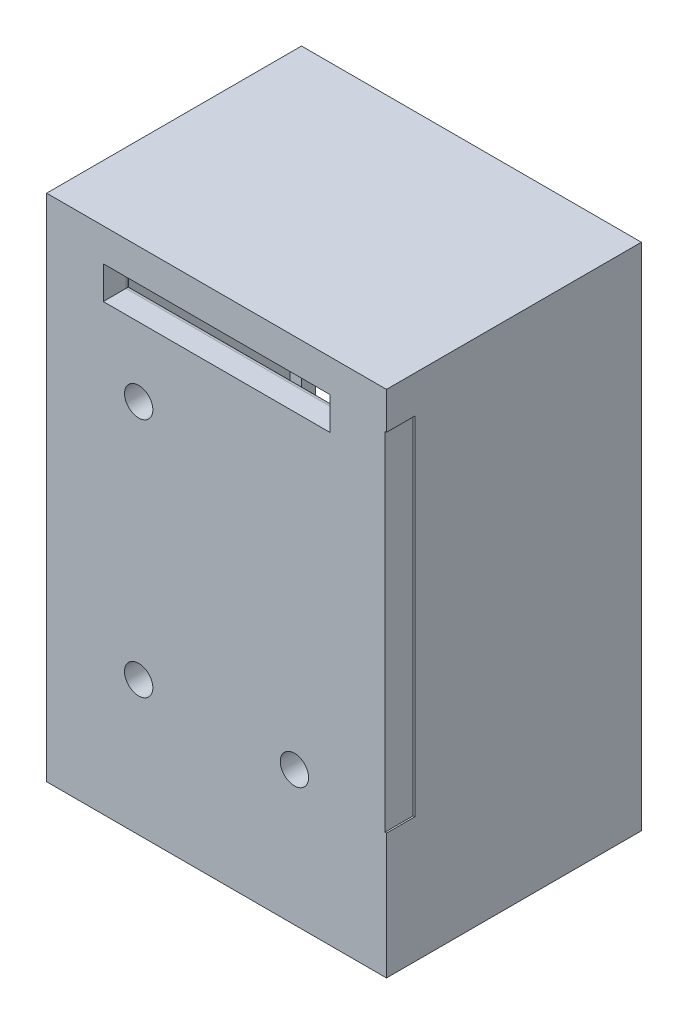
SolidWorks part; units mm, degrees
ref_plane "Plan de face" through (0, 0, 0) normal (0, 0, 1) x (1, 0, 0)
ref_plane "Plan de dessus" through (0, 0, 0) normal (0, 1, 0) x (1, 0, 0)
ref_plane "Plan de droite" through (0, 0, 0) normal (1, 0, 0) x (0, 0, -1)
sketch "Esquisse1" plane through (0, 0, 0) normal (0, 0, 1) x (1, 0, 0)
  line L0 (-42.5, 42.5) -> (0, 0)
  line L1 (-50, 50) -> (50, 50)
  line L2 (-50, 50) -> (-50, -50)
  line L3 (-50, -50) -> (50, -50)
  line L4 (50, 50) -> (50, -50)
  line L5 (-50, 50) -> (50, -50) construction
  line L6 (-50, -50) -> (50, 50) construction
  line L7 (-42.5, 42.5) -> (42.5, 42.5)
  line L8 (-42.5, 42.5) -> (-42.5, -42.5)
  line L9 (-42.5, -42.5) -> (42.5, -42.5)
  line L10 (42.5, 42.5) -> (42.5, -42.5)
  line L11 (-42.5, 42.5) -> (42.5, -42.5) construction
  line L12 (-42.5, -42.5) -> (42.5, 42.5) construction
  line L13 (0, 0) -> (42.5, -42.5)
  line L14 (-42.5, -42.5) -> (0, 0)
  line L15 (0, 0) -> (42.5, 42.5)
  line L16 (-42.5, 42.5) -> (-50, 42.5)
  line L17 (-50, 42.5) -> (-42.5, 50)
  line L18 (-42.5, 50) -> (-42.5, 42.5)
  line L19 (-46.25, 46.25) -> (-44.4822, 48.0178)
  line L20 (-46.25, 46.25) -> (-48.0178, 44.4822)
  line L21 (44.4822, -48.0178) -> (-47.9542, 44.5507)
  line L22 (44.4822, -48.0178) -> (47.9542, -44.5507)
  line L23 (-47.9542, 44.5507) -> (-44.4822, 48.0178)
  line L24 (47.9542, -44.5507) -> (-44.4822, 48.0178)
  line L25 (44.4822, -48.0178) -> (-44.4822, 48.0178) construction
  line L26 (-47.9542, 44.5507) -> (47.9542, -44.5507) construction
  line L27 (42.5, 42.5) -> (42.5, 50)
  line L28 (42.5, 42.5) -> (50, 42.5)
  line L29 (50, 42.5) -> (42.5, 50)
  line L30 (46.25, 46.25) -> (44.3148, 48.1852)
  line L31 (46.25, 46.25) -> (47.8504, 44.6496)
  line L32 (-44.3148, -48.1852) -> (48.1852, 44.3148)
  line L33 (-44.3148, -48.1852) -> (-48.1852, -44.3148)
  line L34 (48.1852, 44.3148) -> (44.3148, 48.1852)
  line L35 (-48.1852, -44.3148) -> (44.3148, 48.1852)
  line L36 (-44.3148, -48.1852) -> (44.3148, 48.1852) construction
  line L37 (48.1852, 44.3148) -> (-48.1852, -44.3148) construction
  circle A0 centre (0, 0) radius 29
  circle A1 centre (0, 0) radius 34
  point P0 (0, 0)
  point P6 (0, 0)
  dimension "D5" = 58
  dimension "D6" = 68
  dimension "D1" = 100
  dimension "D2" = 100
  dimension "D3" = 85
  dimension "D4" = 85
  dimension "D7" = 2.5
  dimension "D8" = 2.5
  dimension "D9" = 5
extrude "Boss.-Extru.2" add sketch "Esquisse1" along normal blind 10 contours L7 L35 L27 L1 L18 L24 | L33 L35 L8 L21 L16 L2 L3 L4 L28 L32 L10 L24 L22 L9 | L21 A1 L35 A0 | L32 A1 L21 A0 | L35 A1 L24 A0 | L24 A1 L32 A0 | A1 L32 L10 L15 | A1 L15 L7 L35 | L15 A1 L35 A0 | L32 A1 L15 A0 | L24 A1 L0 A0 | A1 L24 L7 L0 | L0 A1 L21 A0 | L21 A1 L13 A0 | L13 A1 L24 A0 | A1 L13 L10 L24 | A1 L21 L9 L13 | L22 L24 L10 L9 L21 | L35 L33 L32 L9 L8 | A1 L35 L8 L14 | A1 L14 L9 L32 | L35 A1 L14 A0 | L14 A1 L32 A0 | A1 L0 L8 L21 | L21 L8 L16 | L7 L24 L18 | L18 L24 L17 L20 L21 L16 | L16 L21 L17 | L21 L23 L17 L1 L2 | L24 L18 L17 | L27 L35 L29 | L35 L27 L28 L32 L29 | L32 L28 L29 | L29 L4 L1 | L10 L32 L28 | L35 L7 L27 | L16 L17 L18 region at (-31.9722, 33.7018, 0) region at (-41.3241, 43.6776, 0) region at (-33.6728, 31.9878, 0) region at (-43.6355, 41.3629, 0) region at (-44.7427, 44.7878, 0) region at (-21.3754, 23.1269, 0) region at (-23.111, 21.3913, 0) region at (-0.082, 46.3052, 0) region at (-43.8622, 0.2295, 0) region at (-47.9527, 43.1828, 0) region at (-43.1607, 48.0168, 0) region at (-0.1204, 29.0381, 0) region at (-29.033, 0.1411, 0) region at (41.2099, 43.7901, 0) region at (31.8324, 33.7334, 0) region at (-33.7334, -31.8324, 0) region at (-43.8581, -43.8581, 0) region at (-47.5002, 47.5005, 0) region at (21.2774, 23.2138, 0) region at (-23.2138, -21.2774, 0) region at (43.7901, 41.2099, 0) region at (33.7334, 31.8324, 0) region at (44.8027, 44.8027, 0) region at (43.1049, 48.1852, 0) region at (-31.8324, -33.7334, 0) region at (47.5, 47.5, 0) region at (23.2138, 21.2774, 0) region at (-21.2774, -23.2138, 0) region at (48.1852, 43.1049, 0) region at (29.033, -0.1411, 0) region at (0.1204, -29.0381, 0) region at (43.8779, -43.9513, 0) region at (33.6728, -31.9878, 0) region at (31.9722, -33.7018, 0) region at (23.111, -21.3913, 0) region at (21.3754, -23.1269, 0)
sketch "Esquisse2" plane through (0, 50, 0) normal (0, 1, 0) x (-1, 0, 0)
  line L0 (50, 5) -> (-50, 5)
  line L1 (50, 10) -> (50, 0) construction
  line L2 (-50, 10) -> (-50, 0) construction
  line L4 (2.5, 7.5) -> (-2.5, 7.5)
  line L5 (2.5, 7.5) -> (2.5, 2.5)
  line L6 (2.5, 2.5) -> (-2.5, 2.5)
  line L7 (-2.5, 7.5) -> (-2.5, 2.5)
  line L8 (2.5, 7.5) -> (-2.5, 2.5) construction
  line L9 (2.5, 2.5) -> (-2.5, 7.5) construction
  point P6 (0, 5)
  dimension "D1" = 5
  dimension "D2" = 5
extrude "Boss.-Extru.3" add sketch "Esquisse2" along normal blind 5 contours L0 L7 L6 L5 | L4 L7 L0 L5 region at (0, 50, 3.75) region at (0, 50, 6.25)
sketch "Esquisse3" plane through (0, 55, 0) normal (0, 1, 0) x (-1, 0, 0)
  line L0 (2.5, 5) -> (-2.5, 5)
  line L1 (2.5, 7.5) -> (2.5, 2.5) construction
  line L2 (-2.5, 7.5) -> (-2.5, 2.5) construction
  line L3 (2.5, 5) -> (2.5, 4)
  line L4 (2.5, 4) -> (-2.5, 4)
  line L5 (-2.5, 4) -> (-2.5, 5)
  line L6 (2.5, 5) -> (2.5, 6)
  line L7 (2.5, 6) -> (-2.5, 6)
  line L8 (-2.5, 6) -> (-2.5, 5)
  line M1 (2.5, 2.5) -> (2.5, 7.5)
  line M3 (-2.5, 7.5) -> (-2.5, 2.5)
  dimension "D1" = 1
  dimension "D2" = 1
extrude "Enlèv. mat.-Extru.1" cut sketch "Esquisse3" against normal blind 2 contours L4 L0 M1 M3 | L7 L0 M1 M3 region at (0, 55, 4.5) region at (0, 55, 5.5)
sketch "Esquisse4" plane through (-2.5, 0, 0) normal (-1, 0, 0) x (0, 0, 1)
  line L0 (6, 53) -> (6, 68)
  line L1 (6, 53) -> (4, 53)
  line L2 (4, 53) -> (4, 68)
  line L3 (4, 68) -> (6, 68)
  dimension "D1" = 15
extrude "Boss.-Extru.4" add sketch "Esquisse4" along normal blind 50 and the other way blind 55
sketch "Esquisse5" plane through (0, 0, 6) normal (0, 0, 1) x (1, 0, 0)
  line L0 (52.5, 60.5) -> (12.5, 60.5)
  line L1 (52.5, 53) -> (52.5, 68) construction
  line L2 (-52.5, 60.5) -> (-12.5, 60.5)
  line L3 (52.5, 58.5) -> (12.5, 58.5)
  line L4 (52.5, 58.5) -> (52.5, 62.5)
  line L5 (52.5, 62.5) -> (12.5, 62.5)
  line L6 (12.5, 58.5) -> (12.5, 62.5)
  line L7 (52.5, 58.5) -> (12.5, 62.5) construction
  line L8 (52.5, 62.5) -> (12.5, 58.5) construction
  line L9 (-52.5, 53) -> (-52.5, 68) construction
  line L11 (-52.5, 58.5) -> (-12.5, 58.5)
  line L12 (-52.5, 58.5) -> (-52.5, 62.5)
  line L13 (-52.5, 62.5) -> (-12.5, 62.5)
  line L14 (-12.5, 58.5) -> (-12.5, 62.5)
  line L15 (-52.5, 58.5) -> (-12.5, 62.5) construction
  line L16 (-52.5, 62.5) -> (-12.5, 58.5) construction
  point P4 (32.5, 60.5)
  point P13 (-32.5, 60.5)
  point P14 (-32.5, 60.5)
  line M8 (-52.5, 68) -> (-52.5, 53)
  dimension "D1" = 4
  dimension "D2" = 40
  dimension "D3" = 40
  dimension "D4" = 4
extrude "Enlèv. mat.-Extru.2" cut sketch "Esquisse5" against normal blind 1 contours L2 L14 L13 M8 | L11 L14 L2 M8 | L6 L0 L4 L5 | L6 L3 L4 L0 region at (32.5, 59.5, 6) region at (32.5, 61.5, 6) region at (-32.5, 61.5, 6) region at (-32.5, 59.5, 6)
sketch "Esquisse6" plane through (0, 0, 6) normal (0, 0, 1) x (1, 0, 0)
  line L0 (-52.5, 58.5) -> (-12.5, 58.5) construction
  line L1 (-12.5, 58.5) -> (-32.5, 58.5) construction
  line L2 (-32.5, 58.5) -> (-32.5, 62.5) construction
  line L3 (-52.5, 62.5) -> (-12.5, 62.5) construction
  line L4 (-32.5, 58.5) -> (-12.5, 58.5) construction
  line L5 (-12.5, 58.5) -> (-22.5, 58.5) construction
  line L6 (-22.5, 58.5) -> (-22.5, 62.5) construction
  line L7 (-52.5, 58.5) -> (-32.5, 58.5) construction
  line L8 (-42.5, 58.5) -> (-42.5, 62.5) construction
  line L9 (12.5, 58.5) -> (52.5, 58.5) construction
  line L10 (52.5, 58.5) -> (32.5, 58.5) construction
  line L11 (32.5, 58.5) -> (32.5, 62.5) construction
  line L12 (52.5, 62.5) -> (12.5, 62.5) construction
  line L13 (32.5, 58.5) -> (52.5, 58.5) construction
  line L14 (42.5, 58.5) -> (42.5, 62.5) construction
  line L15 (32.5, 58.5) -> (12.5, 58.5) construction
  line L16 (22.5, 58.5) -> (22.5, 62.5) construction
  line L18 (-44, 56.5) -> (-41, 56.5)
  line L19 (-44, 56.5) -> (-44, 64.5)
  line L20 (-44, 64.5) -> (-41, 64.5)
  line L21 (-41, 56.5) -> (-41, 64.5)
  line L22 (-44, 56.5) -> (-41, 64.5) construction
  line L23 (-44, 64.5) -> (-41, 56.5) construction
  line L24 (-24, 56.5) -> (-21, 56.5)
  line L25 (-24, 56.5) -> (-24, 64.5)
  line L26 (-24, 64.5) -> (-21, 64.5)
  line L27 (-21, 56.5) -> (-21, 64.5)
  line L28 (-24, 56.5) -> (-21, 64.5) construction
  line L29 (-24, 64.5) -> (-21, 56.5) construction
  line L30 (21, 56.5) -> (24, 56.5)
  line L31 (21, 56.5) -> (21, 64.5)
  line L32 (21, 64.5) -> (24, 64.5)
  line L33 (24, 56.5) -> (24, 64.5)
  line L34 (21, 56.5) -> (24, 64.5) construction
  line L35 (21, 64.5) -> (24, 56.5) construction
  line L36 (41, 56.5) -> (44, 56.5)
  line L37 (41, 56.5) -> (41, 64.5)
  line L38 (41, 64.5) -> (44, 64.5)
  line L39 (44, 56.5) -> (44, 64.5)
  line L40 (41, 56.5) -> (44, 64.5) construction
  line L41 (41, 64.5) -> (44, 56.5) construction
  point P24 (-42.5, 60.5)
  point P29 (-22.5, 60.5)
  point P34 (22.5, 60.5)
  point P39 (42.5, 60.5)
  dimension "D1" = 8
  dimension "D2" = 3
  dimension "D3" = 8
  dimension "D4" = 3
  dimension "D5" = 8
  dimension "D6" = 3
  dimension "D7" = 3
  dimension "D8" = 8
extrude "Boss.-Extru.5" add sketch "Esquisse6" along normal blind 2
sketch "Esquisse7" plane through (0, 0, 0) normal (0, 0, -1) x (-1, 0, 0)
  line L0 (-50, 50) -> (50, -50) construction
  line L1 (50, 50) -> (-50, -50) construction
  line L2 (-42.5, -39.0887) -> (-42.5, -42.5) construction
  line L3 (-42.5, -42.5) -> (-38.9723, -42.5) construction
  line L4 (-50, -50) -> (-42.5, -42.5) construction
  line L5 (-42.5, -42.5) -> (-50, -50) construction
  line L6 (-50, -50) -> (-46.25, -46.25) construction
  line L7 (-46.25, -46.25) -> (-46.25, 46.25) construction
  line L8 (-46.25, 46.25) -> (46.217, 46.283) construction
  line L9 (47.9517, 44.5483) -> (44.4822, 48.0178) construction
  line L10 (46.217, 46.283) -> (46.217, -46.217) construction
  line L11 (46.217, -46.217) -> (-46.25, -46.25) construction
  circle A0 centre (-46.25, 46.25) radius 2.5
  circle A1 centre (46.217, 46.283) radius 2.5
  circle A2 centre (46.217, -46.217) radius 2.5
  circle A3 centre (-46.25, -46.25) radius 2.5
  dimension "D1" = 5
  dimension "D2" = 5
  dimension "D3" = 5
  dimension "D4" = 5
extrude "Enlèv. mat.-Extru.3" cut sketch "Esquisse7" against normal blind 10
fillet "Congé1" radius 5 2 edges at (0, 55, 7.5) (0, 55, 2.5)
fillet "Congé4" radius 1 6 edges at (-27.5, 53, 6) (27.5, 53, 6) (27.5, 53, 4) (-27.5, 53, 4) (0, 68, 6) (0, 68, 4)
fillet "Congé5" radius 1 8 edges at (50, 0, 10) (0, -50, 10) (-50, 0, 10) (0, 50, 10) (0, -50, 0) (-50, 0, 0) (0, 50, 0) (50, 0, 0)
fillet "Congé6" radius 1 28 edges at (-49.7071, -49.7071, 9.7071) (-49.7071, -49.7071, 0.2929) (49.7071, -49.7071, 9.7071) (49.7071, -49.7071, 0.2929) (-49.7071, 49.7071, 9.7071) (-49.7071, 49.7071, 0.2929) (49.7071, 49.7071, 9.7071) (49.7071, 49.7071, 0.2929) (-42.5, 0.2295, 0) (-34.1994, -30.3291, 0) (-30.3291, -34.1994, 0) (0.1713, -42.5, 0) (30.5991, -34.1148, 0) (34.0989, -30.6756, 0) (42.5, -0.2295, 0) (34.1994, 30.3291, 0) (30.3291, 34.1994, 0) (-0.1713, 42.5, 0) (-30.5991, 34.1148, 0) (-34.0989, 30.6756, 0) (-33.9997, 0.1543, 0) (-0.13, 33.9998, 0) (33.9997, -0.1543, 0) (0.13, -33.9998, 0) (-50, -50, 5) (50, -50, 5) (-50, 50, 5) (50, 50, 5)
fillet "Congé7" radius 2 8 edges at (42.5, 56.5, 8) (42.5, 64.5, 8) (22.5, 56.5, 8) (22.5, 64.5, 8) (-22.5, 56.5, 8) (-22.5, 64.5, 8) (-42.5, 56.5, 8) (-42.5, 64.5, 8)
sketch "Esquisse8" plane through (0, 50, 0) normal (0, 1, 0) x (-1, 0, 0)
  line L0 (49, 5) -> (-49, 5) construction
  line L1 (49, 1) -> (49, 9) construction
  line L2 (-49, 9) -> (-49, 1) construction
  line L3 (-49, 5) -> (0, 5) construction
  line L4 (0, 5) -> (-24.5, 5) construction
  line L5 (-24.5, 5) -> (-49, 5) construction
  line L6 (-49, 5) -> (-36.75, 5) construction
  line L7 (-36.75, 5) -> (-36.75, 9) construction
  line L8 (49, 9) -> (-49, 9) construction
  line L9 (-36.75, 9) -> (-36.75, 1) construction
  line L10 (-49, 1) -> (49, 1) construction
  line L11 (49, 5) -> (0, 5) construction
  line L12 (0, 5) -> (24.5, 5) construction
  line L13 (24.5, 5) -> (49, 5) construction
  line L14 (49, 5) -> (36.75, 5) construction
  line L15 (36.75, 1) -> (36.75, 9) construction
  line L17 (39.25, 2.5) -> (34.25, 2.5)
  line L18 (39.25, 2.5) -> (39.25, 7.5)
  line L19 (39.25, 7.5) -> (34.25, 7.5)
  line L20 (34.25, 2.5) -> (34.25, 7.5)
  line L21 (39.25, 2.5) -> (34.25, 7.5) construction
  line L22 (39.25, 7.5) -> (34.25, 2.5) construction
  line L23 (-34.25, 2.5) -> (-39.25, 2.5)
  line L24 (-34.25, 2.5) -> (-34.25, 7.5)
  line L25 (-34.25, 7.5) -> (-39.25, 7.5)
  line L26 (-39.25, 2.5) -> (-39.25, 7.5)
  line L27 (-34.25, 2.5) -> (-39.25, 7.5) construction
  line L28 (-34.25, 7.5) -> (-39.25, 2.5) construction
  dimension "D1" = 5
  dimension "D2" = 5
  dimension "D3" = 5
  dimension "D4" = 5
extrude "Boss.-Extru.6" add sketch "Esquisse8" along normal blind 5
fillet "Congé8" radius 5 4 edges at (-36.75, 55, 7.5) (36.75, 55, 7.5) (-36.75, 55, 2.5) (36.75, 55, 2.5)
sketch "Esquisse9" plane through (0, 0, 10) normal (0, 0, 1) x (1, 0, 0)
  line L0 (-46.217, -46.217) -> (0, -46.217) construction
  line L1 (0, -46.217) -> (-105.737, -46.217) construction
  line L2 (0, 0) -> (-223.2664, 0) construction
  line L3 (0, -46.217) -> (0, 0) construction
  line L4 (0, 0) -> (0, 46.5692) construction
  line L5 (0, 46.5692) -> (-46.217, 46.283) construction
  line L6 (-179.1375, 46.283) -> (-46.217, 46.283) construction
  line L7 (-46.217, 46.283) -> (-46.217, -46.217) construction
  line L8 (-46.217, 46.283) -> (-56.217, 46.283) construction
  line L9 (-56.217, 46.283) -> (-56.217, 0) construction
  line L10 (-56.217, 0) -> (-46.217, 0) construction
  line L11 (-56.217, 46.283) -> (-56.217, 23.1415) construction
  line L12 (-56.217, 23.1415) -> (-56.217, 46.283) construction
  line L13 (-56.217, 46.283) -> (-56.217, 34.7123) construction
  line L14 (-56.217, 34.7123) -> (-46.217, 34.7123) construction
  line L15 (-46.217, 34.7123) -> (-46.217, 0) construction
  line L16 (-46.217, 0) -> (-56.217, 0) construction
  line L17 (-56.217, 0) -> (-56.217, 23.1415) construction
  line L18 (-56.217, 23.1415) -> (-56.217, 11.5708) construction
  line L19 (-56.217, 11.5708) -> (-46.217, 11.5708) construction
  line L20 (-56.217, 6.5708) -> (-56.217, -16.5712) construction
  line L21 (-46.217, 11.5708) -> (-56.217, 11.5708)
  line L22 (-46.217, 11.5708) -> (-46.217, 6.5708)
  line L23 (-46.217, 6.5708) -> (-56.217, 6.5708)
  line L24 (-56.217, 11.5708) -> (-56.217, 6.5708)
  line L25 (-46.217, 34.7123) -> (-56.217, 34.7123)
  line L26 (-46.217, 34.7123) -> (-46.217, 39.7123)
  line L27 (-46.217, 39.7123) -> (-56.217, 39.7123)
  line L28 (-56.217, 34.7123) -> (-56.217, 39.7123)
  line L29 (-56.217, 46.283) -> (-116.217, 46.283)
  line L30 (-56.217, 46.283) -> (-56.217, -43.717)
  line L31 (-56.217, -43.717) -> (-116.217, -43.717)
  line L32 (-116.217, 46.283) -> (-116.217, -43.717)
  line L34 (-56.217, -16.5712) -> (-46.217, -16.5712)
  line L35 (-56.217, -16.5712) -> (-56.217, -21.5712)
  line L36 (-56.217, -21.5712) -> (-46.217, -21.5712)
  line L37 (-46.217, -16.5712) -> (-46.217, -21.5712)
  line M4 (-49, 49) -> (-49, -49)
  dimension "D1" = 10
  dimension "D2" = 5
  dimension "D3" = 5
  dimension "D4" = 90
  dimension "D5" = 60
  dimension "D6" = 23.142
  dimension "D7" = 5
extrude "Boss.-Extru.7" add sketch "Esquisse9" against normal blind 5 contours L29 L32 L31 L30 L24 L28 | L30 L36 L34 M4 | L37 L34 L36 M4 | L21 L24 L23 M4 | L23 L22 L21 M4 | L28 L25 L27 M4 | L26 L27 L25 M4 region at (-47.6085, 9.0708, 10) region at (-52.6085, 9.0708, 10) region at (-86.217, 1.283, 10) region at (-47.6085, 37.2123, 10) region at (-52.6085, 37.2123, 10) region at (-52.6085, -19.0712, 10) region at (-47.6085, -19.0712, 10)
sketch "Esquisse10" plane through (0, 0, 5) normal (0, 0, -1) x (-1, 0, 0)
  line L0 (116.217, 1.283) -> (113.717, 1.283) construction
  line L1 (116.217, -43.717) -> (56.217, -43.717) construction
  line L2 (58.717, 6.3504) -> (58.717, 43.783)
  line L3 (58.717, 43.783) -> (86.217, 43.783)
  line L4 (86.217, 43.783) -> (113.717, 43.783)
  line L5 (116.217, 46.283) -> (116.217, -43.717) construction
  line L6 (116.217, 1.283) -> (56.217, 6.5708) construction
  line L7 (56.217, 6.5708) -> (58.717, 6.3504) construction
  line L8 (86.217, 6.283) -> (86.217, 46.283) construction
  line L9 (56.217, 46.283) -> (116.217, 46.283) construction
  line L10 (86.217, 46.283) -> (86.217, -43.717) construction
  line L11 (86.217, -43.717) -> (86.217, -41.217) construction
  line L12 (86.217, 46.283) -> (86.217, 43.783) construction
  line L13 (116.217, 1.283) -> (113.717, 1.283) construction
  line L14 (113.717, 43.783) -> (113.717, 1.283)
  line L15 (113.717, 1.283) -> (113.717, -41.217)
  line L16 (113.717, -41.217) -> (86.217, -41.217)
  line L17 (86.217, -41.217) -> (58.717, -41.217)
  line L18 (58.717, -41.217) -> (58.717, 6.3504)
  line L20 (56.217, 46.283) -> (116.217, 46.283)
  line L21 (56.217, 46.283) -> (56.217, -43.717)
  line L22 (56.217, -43.717) -> (116.217, -43.717)
  line L23 (116.217, 46.283) -> (116.217, -43.717)
  dimension "D1" = 2.5
  dimension "D2" = 2.5
  dimension "D3" = 2.5
  dimension "D4" = 2.5
extrude "Boss.-Extru.8" add sketch "Esquisse10" along normal blind 40
sketch "Esquisse13" plane through (0, 0, 5) normal (0, 0, -1) x (-1, 0, 0)
  circle A0 centre (77.258, 24.183) radius 1.4
  circle A1 centre (105.208, 24.183) radius 1.4
  circle A2 centre (62.108, -26.617) radius 1.4
  dimension "D1" = 2.8
  dimension "D2" = 2.8
  dimension "D3" = 2.8
extrude "Boss.-Extru.10" add sketch "Esquisse13" along normal blind 5
sketch "Esquisse14" plane through (0, 0, 5) normal (0, 0, -1) x (-1, 0, 0)
  circle A0 centre (110.408, -28.017) radius 1.4
  dimension "D1" = 2.8
extrude "Boss.-Extru.11" add sketch "Esquisse14" along normal blind 5
sketch "Esquisse15" plane through (0, -43.717, 0) normal (0, -1, 0) x (1, 0, 0)
  line L0 (-104.1082, 4.35) -> (-104.1082, 3.35) construction
  line L1 (-100.408, -7.45) -> (-109.108, -7.45)
  line L2 (-100.408, -7.45) -> (-100.408, 3.35)
  line L3 (-100.408, 3.35) -> (-109.108, 3.35)
  line L4 (-109.108, -7.45) -> (-109.108, 3.35)
  line L5 (-99.408, -8.45) -> (-110.108, -8.45)
  line L6 (-99.408, -8.45) -> (-99.408, 4.35)
  line L7 (-99.408, 4.35) -> (-110.108, 4.35)
  line L8 (-110.108, -8.45) -> (-110.108, 4.35)
  line L9 (-104.1082, 3.35) -> (-104.1082, -7.45) construction
  line L10 (-104.1082, -7.45) -> (-104.1082, -8.45) construction
  line L11 (-99.408, -0.9666) -> (-100.408, -0.9666) construction
  line L12 (-100.408, -0.9666) -> (-109.108, -0.9666) construction
  line L13 (-109.108, -0.9666) -> (-110.108, -0.9666) construction
  line L15 (-100.408, -7.45) -> (-109.108, -7.45)
  line L16 (-100.408, -7.45) -> (-100.408, 3.35)
  line L17 (-100.408, 3.35) -> (-109.108, 3.35)
  line L18 (-109.108, -7.45) -> (-109.108, 3.35)
  dimension "D1" = 1
  dimension "D2" = 1
  dimension "D3" = 1
  dimension "D4" = 1
extrude "Enlèv. mat.-Extru.5" cut sketch "Esquisse15" against normal blind 5 contours L4 L1 L2 L3 | L8 L5 L6 L7 L1 L4 L3 L2 region at (-104.758, -43.717, -2.05) region at (-104.758, -43.717, -8.2832)
sketch "Esquisse16" plane through (0, -43.717, 0) normal (0, -1, 0) x (1, 0, 0)
  line L0 (-74.708, 3.45) -> (-74.708, 4.45) construction
  line L1 (-80.658, 3.45) -> (-68.758, 3.45)
  line L2 (-80.658, 3.45) -> (-80.658, -7.15)
  line L3 (-80.658, -7.15) -> (-68.758, -7.15)
  line L4 (-68.758, 3.45) -> (-68.758, -7.15)
  line L5 (-74.708, 4.45) -> (-74.708, -7.15) construction
  line L6 (-74.708, -7.15) -> (-74.708, -8.15) construction
  line L7 (-80.658, -1.85) -> (-74.708, -1.85) construction
  line L8 (-74.708, -1.85) -> (-68.758, -1.85) construction
  line L9 (-68.758, -1.85) -> (-67.758, -1.85) construction
  line L10 (-67.758, -1.85) -> (-80.658, -1.85) construction
  line L11 (-80.658, -1.85) -> (-81.658, -1.85) construction
  line L12 (-81.658, -1.85) -> (-81.658, 4.45) construction
  line L13 (-81.658, 4.45) -> (-74.708, 4.45) construction
  line L14 (-74.708, 4.45) -> (-67.758, 4.45) construction
  line L15 (-67.758, 4.45) -> (-67.758, -1.85) construction
  line L16 (-67.758, -1.85) -> (-67.758, -8.15) construction
  line L17 (-67.758, -8.15) -> (-74.708, -8.15) construction
  line L18 (-74.708, -8.15) -> (-81.658, -8.15) construction
  line L19 (-81.658, -8.15) -> (-81.658, -1.85) construction
  line L21 (-81.658, 4.45) -> (-67.758, 4.45)
  line L22 (-81.658, 4.45) -> (-81.658, -8.15)
  line L23 (-81.658, -8.15) -> (-67.758, -8.15)
  line L24 (-67.758, 4.45) -> (-67.758, -8.15)
  line L25 (-80.658, 3.45) -> (-68.758, 3.45)
  line L26 (-80.658, 3.45) -> (-80.658, -7.15)
  line L27 (-80.658, -7.15) -> (-68.758, -7.15)
  line L28 (-68.758, 3.45) -> (-68.758, -7.15)
  dimension "D1" = 1
  dimension "D2" = 1
  dimension "D3" = 1
  dimension "D4" = 1
extrude "Enlèv. mat.-Extru.6" cut sketch "Esquisse16" against normal blind 5 contours L4 L1 L2 L3 | L24 L21 L22 L23 L1 L4 L3 L2 region at (-74.708, -43.717, -1.85) region at (-74.708, -43.717, 4.2624)
sketch "Esquisse17" plane through (0, 0, 5) normal (0, 0, -1) x (-1, 0, 0)
  line L0 (116.217, 46.283) -> (56.217, 46.283) construction
  line L1 (56.217, 46.283) -> (116.217, 46.283) construction
  line L2 (56.217, 46.283) -> (56.217, 39.7123) construction
  line L3 (56.217, 46.283) -> (56.217, 34.7123) construction
  line L4 (56.217, 34.7123) -> (116.217, 34.7123) construction
  line L5 (116.217, 46.283) -> (116.217, -43.717) construction
  line L6 (116.217, 34.7123) -> (116.217, 46.283) construction
  line L7 (116.217, 46.283) -> (116.217, 1.283) construction
  line L8 (116.217, 1.283) -> (56.217, 1.283) construction
  line L9 (56.217, 6.5708) -> (56.217, -16.5712) construction
  line L10 (56.217, 1.283) -> (56.217, 34.7123) construction
  line L11 (56.217, 34.7123) -> (116.217, 1.283) construction
  line L12 (116.217, 1.283) -> (116.217, 34.7123) construction
  line L13 (116.217, 34.7123) -> (56.217, 1.283) construction
  line L14 (116.217, 34.7123) -> (116.217, 40.4976) construction
  line L15 (116.217, 40.4976) -> (56.217, 40.4976) construction
  line L16 (56.217, 40.4976) -> (56.217, 34.7123) construction
  line L17 (116.217, 40.4976) -> (106.217, 40.4976) construction
  line L18 (106.217, 40.4976) -> (106.217, 34.7123) construction
  line L19 (56.217, 40.4976) -> (66.217, 40.4976) construction
  line L20 (66.217, 40.4976) -> (66.217, 34.7123) construction
  line L22 (106.217, 40.4976) -> (66.217, 40.4976)
  line L23 (106.217, 40.4976) -> (106.217, 34.7123)
  line L24 (106.217, 34.7123) -> (66.217, 34.7123)
  line L25 (66.217, 40.4976) -> (66.217, 34.7123)
  dimension "D1" = 10
  dimension "D2" = 10
extrude "Enlèv. mat.-Extru.7" cut sketch "Esquisse17" against normal blind 5
fillet "Congé10" radius 1 4 edges at (-106.217, 37.6049, 5) (-86.217, 34.7123, 5) (-66.217, 37.6049, 5) (-86.217, 40.4976, 5)
sketch "Esquisse20" plane through (-116.217, 0, 0) normal (-1, 0, 0) x (0, 0, 1)
  line L1 (-35, 46.283) -> (10, 46.283) construction
  line L2 (-32.5, 46.283) -> (-32.5, 44.783) construction
  line L3 (-35, -43.717) -> (-32.5, -43.717) construction
  line L4 (-35, -43.717) -> (10, -43.717) construction
  line L5 (-32.5, -43.717) -> (-32.5, -42.217) construction
  line L7 (-32.5, -42.217) -> (-30.5, -42.217)
  line L8 (-32.5, -42.217) -> (-32.5, 44.783)
  line L9 (-32.5, 44.783) -> (-30.5, 44.783)
  line L10 (-30.5, -42.217) -> (-30.5, 44.783)
  dimension "D1" = 1.5
  dimension "D2" = 2
  dimension "D3" = 1.5
  dimension "D4" = 2.5
extrude "Enlèv. mat.-Extru.10" cut sketch "Esquisse20" against normal blind 58.5
sketch "Esquisse21" plane through (50, 0, 0) normal (1, 0, 0) x (0, 0, -1)
  line L0 (-9, 49) -> (-9, -49) construction
  line L1 (-9, 44.2245) -> (-1, 44.2245)
  line L2 (-9, 44.2245) -> (-9, 36.5324)
  line L3 (-9, 36.5324) -> (-1, 36.5324)
  line L4 (-1, 44.2245) -> (-1, 36.5324)
  line L5 (-1, -49) -> (-1, 49) construction
  line L7 (-9, -34.3741) -> (-1, -34.3741)
  line L8 (-9, -34.3741) -> (-9, -41.3595)
  line L9 (-9, -41.3595) -> (-1, -41.3595)
  line L10 (-1, -34.3741) -> (-1, -41.3595)
extrude "Boss.-Extru.17" add sketch "Esquisse21" along normal blind 10
sketch "Esquisse29" plane through (60, 0, 0) normal (1, 0, 0) x (0, 0, -1)
  line L1 (-9, 49.4493) -> (36.0244, 49.4493)
  line L2 (-9, 49.4493) -> (-9, -48.2057)
  line L3 (-9, -48.2057) -> (36.0244, -48.2057)
  line L4 (36.0244, 49.4493) -> (36.0244, -48.2057)
extrude "Boss.-Extru.19" [suppressed] add sketch "Esquisse29" along normal blind 100
sketch "Esquisse30" [suppressed] plane through (0, 0, -36.0244) normal (0, 0, -1) x (-1, 0, 0)
  line L1 (-156.3216, 44.7075) -> (-64.9621, 44.7075)
  line L2 (-156.3216, 44.7075) -> (-156.3216, -43.3176)
  line L3 (-156.3216, -43.3176) -> (-64.9621, -43.3176)
  line L4 (-64.9621, 44.7075) -> (-64.9621, -43.3176)
extrude "Enlèv. mat.-Extru.12" [suppressed] cut sketch "Esquisse30" against normal blind 37
sketch "Esquisse31" [suppressed] plane through (0, -48.2057, 0) normal (0, -1, 0) x (1, 0, 0)
  line L0 (160, -36.0244) -> (60, 9) construction
  line L1 (60, 9) -> (60, -36.0244) construction
  line L2 (60, -36.0244) -> (160, 9) construction
  line L3 (110, -13.5122) -> (60, 9) construction
  line L4 (110, -13.5122) -> (110, 9) construction
  line L5 (160, 9) -> (60, 9) construction
  line L6 (110, 9) -> (110, -13.5122) construction
  line L7 (110, -13.5122) -> (60, -13.5122) construction
  line L8 (60, -13.5122) -> (110, 9) construction
  line L9 (110, 9) -> (85, -2.2561) construction
  line L11 (96.9434, -7.6335) -> (73.0566, -7.6335)
  line L12 (96.9434, -7.6335) -> (96.9434, 3.1214)
  line L13 (96.9434, 3.1214) -> (73.0566, 3.1214)
  line L14 (73.0566, -7.6335) -> (73.0566, 3.1214)
  line L15 (96.9434, -7.6335) -> (73.0566, 3.1214) construction
  line L16 (96.9434, 3.1214) -> (73.0566, -7.6335) construction
extrude "Enlèv. mat.-Extru.13" [suppressed] cut sketch "Esquisse31" against normal blind 10
fillet "Congé15" [suppressed] radius 10
sketch "Esquisse36" plane through (-50, 0, 0) normal (-1, 0, 0) x (0, 0, 1)
  line L0 (9, -50) -> (1, -50) construction
  line L1 (-4, -49) -> (21, -49)
  line L2 (-4, -49) -> (-4, 101)
  line L3 (-4, 101) -> (21, 101)
  line L4 (21, -49) -> (21, 101)
  dimension "D1" = 25
  dimension "D2" = 5
  dimension "D3" = 150
  dimension "D4" = 1
extrude "Enlèv. mat.-Extru.17" cut sketch "Esquisse36" against normal blind 110
sketch "Esquisse37" plane through (-50, 0, 0) normal (1, 0, 0) x (0, 0, -1)
  line L1 (-5, 39.7123) -> (-10, 39.7123)
  line L2 (-5, 39.7123) -> (-5, -21.5712)
  line L3 (-5, -21.5712) -> (-10, -21.5712)
  line L4 (-10, 39.7123) -> (-10, -21.5712)
extrude "Enlèv. mat.-Extru.20" cut sketch "Esquisse37" against normal blind 6.5
sketch "Esquisse38" plane through (0, 0, 5) normal (0, 0, -1) x (-1, 0, 0)
  line L0 (58.717, 43.783) -> (113.717, -41.217) construction
  line L1 (113.717, -41.217) -> (86.217, 1.283) construction
  line L2 (86.217, 1.283) -> (113.717, 43.783) construction
  line L3 (113.717, 43.783) -> (58.717, -41.217) construction
  line L4 (58.717, 43.783) -> (58.717, -41.217) construction
  line L5 (58.717, -41.217) -> (113.717, -41.217) construction
  line L6 (58.717, -41.217) -> (86.217, 1.283) construction
  line L7 (86.217, 1.283) -> (72.467, -19.967) construction
  line L8 (72.467, -19.967) -> (99.967, -19.967) construction
  line L9 (99.967, -19.967) -> (99.967, 22.533) construction
  line L10 (99.967, 22.533) -> (72.467, 22.533) construction
  line L11 (72.467, 22.533) -> (72.467, -19.967) construction
  circle A0 centre (99.967, 22.533) radius 2.5
  circle A1 centre (99.967, -19.967) radius 2.5
  circle A2 centre (72.467, -19.967) radius 2.5
  dimension "D1" = 5
  dimension "D2" = 5
  dimension "D3" = 5
extrude "Enlèv. mat.-Extru.21" cut sketch "Esquisse38" against normal blind 6.5
